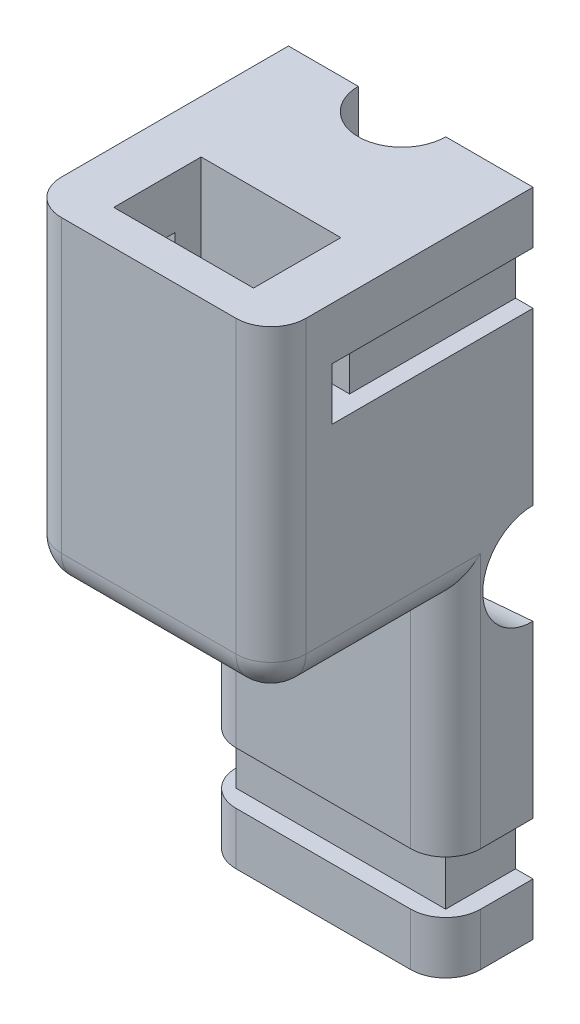
SolidWorks part; units mm, degrees
ref_plane "Alzado" through (0, 0, 0) normal (0, 0, 1) x (1, 0, 0)
ref_plane "Planta" through (0, 0, 0) normal (0, 1, 0) x (1, 0, 0)
ref_plane "Vista lateral" through (0, 0, 0) normal (1, 0, 0) x (0, 0, -1)
sketch "Croquis1" plane through (0, 0, 0) normal (0, 0, 1) x (1, 0, 0)
  line L0 (0, 7) -> (0, -7)
  line L1 (0, -7) -> (0, -10)
  line L2 (0, 0) -> (-3.5, 0) construction
  line L3 (-3.5, 7) -> (-3.5, -7)
  line L4 (-3.5, -7) -> (-2.5, -9.6451)
  line L5 (-2.5, -9.6451) -> (-2.5, -18.6451)
  line L6 (-2.5, -18.6451) -> (-0.8, -18.6451)
  line L12 (0, 7) -> (0, 10)
  line L18 (-2.5, 18.6451) -> (-0.8, 18.6451)
  line L19 (-2.5, 9.6451) -> (-2.5, 18.6451)
  line L20 (-3.5, 7) -> (-2.5, 9.6451)
  dimension "D1" = 7
  dimension "D2" = 3
  dimension "D3" = 7
  dimension "D4" = 9
  dimension "D5" = 2.5
  dimension "D6" = 3.5
  dimension "D7" = 1.7
ref_plane "Plano1" through (0, 0, 0) normal (0, 0, 1) x (1, 0, 0)
sketch "Croquis2" plane through (0, 0, 0) normal (0, 0, 1) x (1, 0, 0)
  line L0 (0, 18.6451) -> (-2.5, 18.6451)
  line L1 (-2.5, 18.6451) -> (-2.5, 9.6451)
  line L2 (-2.5, 9.6451) -> (-3.5, 7)
  line L3 (-3.5, 7) -> (-3.5, -7)
  line L4 (-3.5, -7) -> (-2.5, -9.6451)
  line L5 (-2.5, -9.6451) -> (-2.5, -18.6451)
  line L6 (-2.5, -18.6451) -> (0, -18.6451)
  line L7 (0, -18.6451) -> (0, 18.6451)
  line L9 (-6.5, 18.6451) -> (7.5, 18.6451)
  line L10 (-6.5, 18.6451) -> (-6.5, -18.6451)
  line L11 (-6.5, -18.6451) -> (7.5, -18.6451)
  line L12 (7.5, 18.6451) -> (7.5, -18.6451)
  dimension "D1" = 7.5
  dimension "D2" = 3
extrude "Saliente-Extruir1" add sketch "Croquis2" along normal blind 5 contours L12 L11 L10 L9
revolve "Cortar-Revolución1" cut sketch "Croquis2<4>" angle 360 about L12 region at (-1.5111, 0, 0)
sketch "Croquis2<4>" plane through (0, 0, 0) normal (0, 0, 1) x (1, 0, 0) same geometry as "Croquis2"
sketch "Croquis3" plane through (0, 0, 0) normal (0, 0, -1) x (-1, 0, 0)
  line L0 (0, 0) -> (0, 3.5)
  line L1 (0, 7) -> (0, -7) construction
  line L2 (0, 0) -> (-12, 0)
  line L3 (-12, 0) -> (-12, 2.5)
  line L4 (-12, 2.5) -> (0, 3.5)
  dimension "D1" = 3.5
  dimension "D2" = 2.5
  dimension "D3" = 12
revolve "Cortar-Revolución2" cut sketch "Croquis3" angle 360 about L2
sketch "Croquis6" plane through (0, 0, 5) normal (0, 0, 1) x (1, 0, 0)
  line L0 (7.5, 18.6451) -> (7.5, -18.6451) construction
  line L1 (7.5, 0) -> (-6.5, 0)
  line L2 (7.5, 0) -> (7.5, 18.6451)
  line L3 (7.5, 18.6451) -> (-6.5, 18.6451)
  line L4 (-6.5, 0) -> (-6.5, 18.6451)
extrude "Saliente-Extruir2" add sketch "Croquis6" along normal blind 10
sketch "Croquis4" plane through (0, 0, 0) normal (0, 0, -1) x (-1, 0, 0)
  line L0 (-7.5, 18.6451) -> (-7.5, 2.875) construction
  line L1 (-7.5, 15.6451) -> (-6.5, 15.6451)
  line L2 (-7.5, 15.6451) -> (-7.5, 12.6451)
  line L3 (-7.5, 12.6451) -> (-6.5, 12.6451)
  line L4 (-6.5, 15.6451) -> (-6.5, 12.6451)
  line L5 (-2.5, 18.6451) -> (-7.5, 18.6451) construction
  line L6 (5.5, 15.6451) -> (6.5, 15.6451)
  line L7 (5.5, 15.6451) -> (5.5, 12.6451)
  line L8 (5.5, 12.6451) -> (6.5, 12.6451)
  line L9 (6.5, 15.6451) -> (6.5, 12.6451)
  line L10 (5.5, -12.6451) -> (6.5, -12.6451)
  line L11 (5.5, -12.6451) -> (5.5, -15.6451)
  line L12 (5.5, -15.6451) -> (6.5, -15.6451)
  line L13 (6.5, -12.6451) -> (6.5, -15.6451)
  line L14 (-7.5, -12.6451) -> (-6.5, -12.6451)
  line L15 (-7.5, -12.6451) -> (-7.5, -15.6451)
  line L16 (-7.5, -15.6451) -> (-6.5, -15.6451)
  line L17 (-6.5, -12.6451) -> (-6.5, -15.6451)
  line L18 (-2.5, -18.6451) -> (-7.5, -18.6451) construction
  dimension "D1" = 1
  dimension "D2" = 3
  dimension "D3" = 3
  dimension "D6" = 3
  dimension "D4" = 2
  dimension "D5" = 2
extrude "Cortar-Extruir2" cut sketch "Croquis4" against normal blind 9.5
sketch "Croquis5" plane through (6.5, 0, 0) normal (1, 0, 0) x (0, 0, -1)
  line L0 (-9.5, 15.6451) -> (0, 15.6451) construction
  line L1 (-11.5, 12.6451) -> (-9.5, 12.6451)
  line L2 (-11.5, 12.6451) -> (-11.5, 15.6451)
  line L3 (-11.5, 15.6451) -> (-9.5, 15.6451)
  line L4 (-9.5, 12.6451) -> (-9.5, 15.6451)
  line L5 (-5, -15.6451) -> (-5, -12.6451) construction
  line L6 (-7.9583, -12.6451) -> (-7.9583, -15.6451)
  line L7 (-4, -15.6451) -> (-7.9583, -15.6451)
  line L8 (-4, -12.6451) -> (-4, -15.6451)
  line L9 (-4, -12.6451) -> (-7.9583, -12.6451)
  line L10 (0, 12.6451) -> (0, 15.6451) construction
  dimension "D1" = 2
  dimension "D2" = 9.5
  dimension "D3" = 1
extrude "Cortar-Extruir3" cut sketch "Croquis5" against normal up to vertex (13 mm away) and the other way up to vertex (1 mm away) up to point (-6.5, 18.6451, 15) other way up to point (7.5, 18.6451, 15)
sketch "Croquis7" plane through (0, 18.6451, 0) normal (0, 1, 0) x (1, 0, 0)
  line L0 (7.5, -15) -> (-6.5, -15) construction
  line L1 (4.5, -13) -> (-3.5, -13)
  line L2 (4.5, -13) -> (4.5, -8)
  line L3 (4.5, -8) -> (-3.5, -8)
  line L4 (-3.5, -13) -> (-3.5, -8)
  line L5 (-6.5, -15) -> (-6.5, 0) construction
  dimension "D1" = 8
  dimension "D2" = 5
  dimension "D3" = 2
  dimension "D4" = 3
extrude "Cortar-Extruir4" cut sketch "Croquis7" against normal blind 15
fillet "Redondeo1" radius 2 9 edges at (7.5, 0, 10) (-6.5, 0, 10) (0.5, 0, 15) (7.5, 9.3225, 15) (-6.5, 9.3225, 15) (7.5, -17.1451, 5) (-6.5, -17.1451, 5) (7.5, -6.3225, 5) (-6.5, -6.3225, 5)
